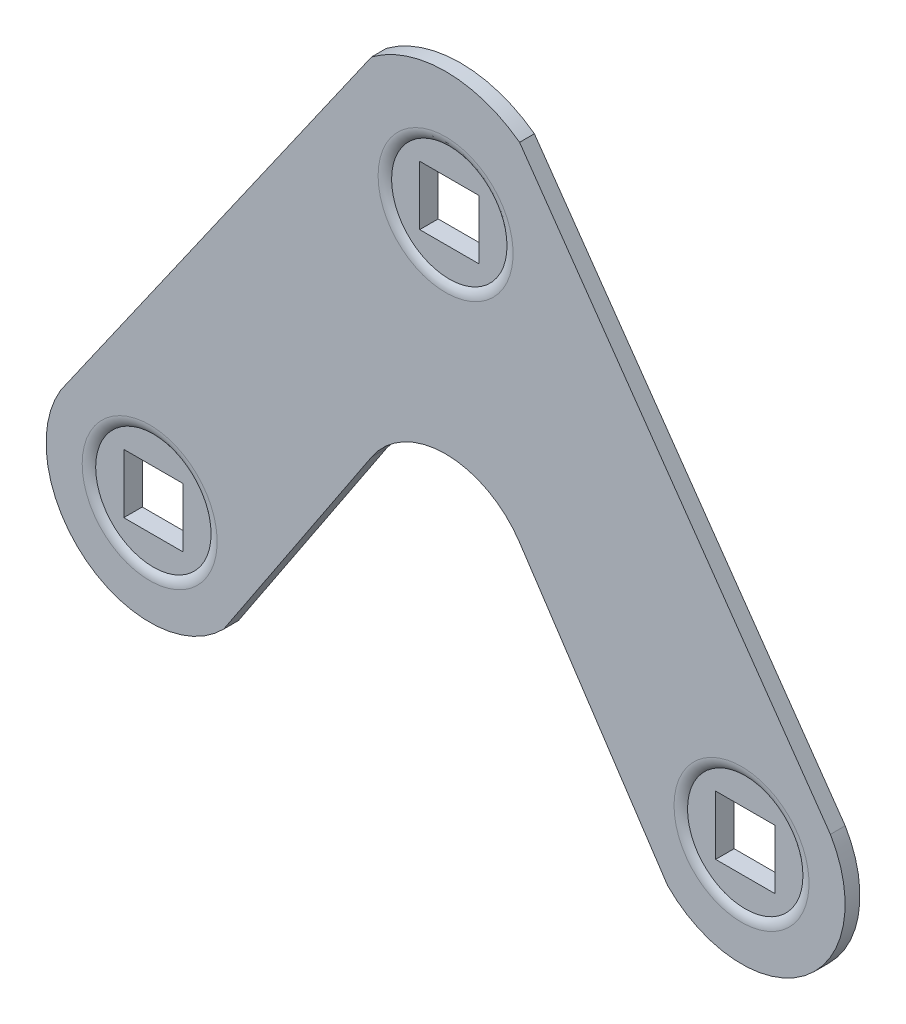
SolidWorks part; units mm, degrees
material "Alumina"
ref_plane "Front Plane" through (0, 0, 0) normal (0, 0, 1) x (1, 0, 0)
ref_plane "Top Plane" through (0, 0, 0) normal (0, 1, 0) x (1, 0, 0)
ref_plane "Right Plane" through (0, 0, 0) normal (1, 0, 0) x (0, 0, -1)
sketch "Sketch1" plane through (0, 0, 0) normal (0, 0, 1) x (1, 0, 0)
  line L0 (0, -23.2365) -> (0, 23.2365) construction
  line L1 (-5, 12.3166) -> (-15, -2.7589)
  line L2 (5, 12.3166) -> (15, -2.7589)
  line L4 (-5, 35.7352) -> (-26.0062, 5.7352)
  line L5 (5, 35.7352) -> (26.0062, 5.7352)
  arc A0 (-5, 12.3166) -> (5, 12.3166) centre (0, 9) cw
  arc A1 (15, -2.7589) -> (26.0062, 5.7352) centre (20, 2.14) ccw
  arc A2 (-15, -2.7589) -> (-26.0062, 5.7352) centre (-20, 2.14) cw
  arc A3 (-5, 35.7352) -> (5, 35.7352) centre (0, 29) cw
  dimension "D3" = 6
  dimension "D6" = 10
  dimension "D7" = 7
  dimension "D1" = 20
  dimension "D9" = 29
  dimension "D2" = 10
  dimension "D4" = 30
  dimension "D5" = 30
  dimension "D8" = 40
  dimension "D10" = 70
extrude "Boss-Extrude2" add sketch "Sketch1" along normal blind 1
sketch "Sketch2" plane through (0, 0, 1) normal (0, 0, 1) x (1, 0, 0)
  circle A0 centre (-20, 2.14) radius 3.9
  circle A1 centre (20, 2.14) radius 3.9
  circle A2 centre (0, 29) radius 3.9
  dimension "D1" = 7.8
  dimension "D2" = 7.8
  dimension "D3" = 7.8
extrude "Cut-Extrude1" cut sketch "Sketch2" against normal blind 0.25
fillet "Fillet1" radius 1 3 edges at (-16.1, 2.14, 1) (23.9, 2.14, 1) (3.9, 29, 1)
sketch "Sketch5" plane through (0, 0, 1) normal (0, 0, 1) x (1, 0, 0)
  line L1 (-2, 31) -> (2, 31)
  line L2 (-2, 31) -> (-2, 27)
  line L3 (-2, 27) -> (2, 27)
  line L4 (2, 31) -> (2, 27)
  line L5 (-2, 31) -> (2, 27) construction
  line L6 (-2, 27) -> (2, 31) construction
  line L7 (18, 4.14) -> (22, 4.14)
  line L8 (18, 4.14) -> (18, 0.14)
  line L9 (18, 0.14) -> (22, 0.14)
  line L10 (22, 4.14) -> (22, 0.14)
  line L11 (18, 4.14) -> (22, 0.14) construction
  line L12 (18, 0.14) -> (22, 4.14) construction
  line L13 (-22, 4.14) -> (-18, 4.14)
  line L14 (-22, 4.14) -> (-22, 0.14)
  line L15 (-22, 0.14) -> (-18, 0.14)
  line L16 (-18, 4.14) -> (-18, 0.14)
  line L17 (-22, 4.14) -> (-18, 0.14) construction
  line L18 (-22, 0.14) -> (-18, 4.14) construction
  point P0 (0, 29)
  point P6 (20, 2.14)
  point P12 (-20, 2.14)
  dimension "D1" = 4
  dimension "D2" = 4
  dimension "D3" = 4
  dimension "D4" = 4
  dimension "D5" = 4
  dimension "D6" = 4
extrude "Cut-Extrude6" cut sketch "Sketch5" against normal blind 2
sketch "Sketch6" plane through (0, 0, 0) normal (0, 0, -1) x (-1, 0, 0)
  line L0 (-18, 0.14) -> (-18, 4.14) construction
  line L1 (-22, 4.14) -> (-18, 4.14)
  line L2 (-22, 4.14) -> (-22, 0.14)
  line L3 (-22, 0.14) -> (-18, 0.14)
  line L4 (-18, 4.14) -> (-18, 0.14)
  line L5 (-22, 4.14) -> (-18, 0.14) construction
  line L6 (-22, 0.14) -> (-18, 4.14) construction
  line L7 (-22, 0.14) -> (-18, 0.14) construction
  line L9 (-2, 31) -> (2, 31)
  line L10 (-2, 31) -> (-2, 27)
  line L11 (-2, 27) -> (2, 27)
  line L12 (2, 31) -> (2, 27)
  line L13 (-2, 31) -> (2, 27) construction
  line L14 (-2, 27) -> (2, 31) construction
  line L15 (18, 4.14) -> (22, 4.14)
  line L16 (18, 4.14) -> (18, 0.14)
  line L17 (18, 0.14) -> (22, 0.14)
  line L18 (22, 4.14) -> (22, 0.14)
  line L19 (18, 4.14) -> (22, 0.14) construction
  line L20 (18, 0.14) -> (22, 4.14) construction
  circle A0 centre (0, 29) radius 4.25
  circle A1 centre (-20, 2.14) radius 4.25
  circle A2 centre (20, 2.14) radius 4.25
  dimension "D1" = 8.5
  dimension "D2" = 8.5
  dimension "D3" = 8.5
  dimension "D4" = 40
  dimension "D5" = 26.86
  dimension "D6" = 33.4882
  dimension "D7" = 4
  dimension "D8" = 4
extrude "Boss-Extrude3" add sketch "Sketch6" along normal blind 0.5
fillet "Fillet2" radius 1 3 edges at (15.75, 2.14, -0.5) (-24.25, 2.14, -0.5) (-4.25, 29, -0.5)
